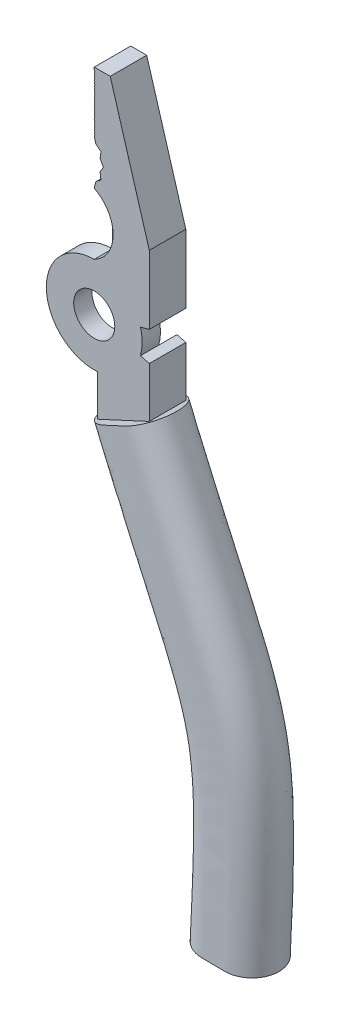
SolidWorks part; units mm, degrees
ref_plane "Front Plane" through (0, 0, 0) normal (0, 0, 1) x (1, 0, 0)
ref_plane "Top Plane" through (0, 0, 0) normal (0, 1, 0) x (1, 0, 0)
ref_plane "Right Plane" through (0, 0, 0) normal (1, 0, 0) x (0, 0, -1)
sketch "Sketch1" plane through (0, 0, 0) normal (0, 0, 1) x (1, 0, 0)
  line L0 (-6.1652, 3.7232) -> (-2.6652, 3.7232)
  line L1 (-2.6652, 3.7232) -> (5.9089, -25.0255)
  line L2 (-6.1652, 3.7232) -> (-6.1652, 3.2232)
  line L3 (-6.1652, 3.2232) -> (-6.0208, 2.9732)
  line L4 (-6.0208, 2.9732) -> (-6.1652, 2.7232)
  line L5 (-6.1652, 2.7232) -> (-6.0208, 2.4732)
  line L6 (-6.0208, 2.4732) -> (-6.1652, 2.2232)
  line L7 (-6.1652, 2.2232) -> (-6.0208, 1.9732)
  line L8 (-6.0208, 1.9732) -> (-6.1652, 1.7232)
  line L9 (-6.1652, 1.7232) -> (-6.0208, 1.4732)
  line L10 (-6.0208, 1.4732) -> (-6.1652, 1.2232)
  line L11 (-6.1652, 1.2232) -> (-6.0208, 0.9732)
  line L12 (-6.0208, 0.9732) -> (-6.1652, 0.7232)
  line L13 (-6.1652, 0.7232) -> (-6.0208, 0.4732)
  line L14 (-6.0208, 0.4732) -> (-6.1652, 0.2232)
  line L15 (-6.1652, 0.2232) -> (-6.0208, -0.0268)
  line L16 (-6.0208, -0.0268) -> (-6.1652, -0.2768)
  line L17 (-6.1652, -0.2768) -> (-6.0208, -0.5268)
  line L18 (-6.0208, -0.5268) -> (-6.1652, -0.7768)
  line L19 (-6.1652, -0.7768) -> (-6.0208, -1.0268)
  line L20 (-6.0208, -1.0268) -> (-6.1652, -1.2768)
  line L21 (-6.1652, -1.2768) -> (-6.0208, -1.5268)
  line L22 (-6.0208, -1.5268) -> (-6.1652, -1.7768)
  line L23 (-6.1652, -1.7768) -> (-6.0208, -2.0268)
  line L24 (-6.0208, -2.0268) -> (-6.1652, -2.2768)
  line L25 (-6.1652, -2.2768) -> (-6.0208, -2.5268)
  line L26 (-6.0208, -2.5268) -> (-6.1652, -2.7768)
  line L27 (-6.1652, -2.7768) -> (-6.0208, -3.0268)
  line L28 (-6.0208, -3.0268) -> (-6.1652, -3.2768)
  line L29 (-6.1652, -3.2768) -> (-6.0208, -3.5268)
  line L30 (-6.0208, -3.5268) -> (-6.1652, -3.7768)
  line L31 (-6.1652, -3.7768) -> (-6.0208, -4.0268)
  line L32 (-6.0208, -4.0268) -> (-6.1652, -4.2768)
  line L33 (-6.1652, -4.2768) -> (-6.0208, -4.5268)
  line L34 (-6.0208, -4.5268) -> (-6.1652, -4.7768)
  line L35 (-6.1652, -4.7768) -> (-6.0208, -5.0268)
  line L36 (-6.0208, -5.0268) -> (-6.1652, -5.2768)
  line L37 (-6.1652, -5.2768) -> (-6.0208, -5.5268)
  line L38 (-6.0208, -5.5268) -> (-6.1652, -5.7768)
  line L39 (-6.1652, -5.7768) -> (-6.0208, -6.0268)
  line L40 (-6.0208, -6.0268) -> (-6.1652, -6.2768)
  line L41 (-6.1652, -6.2768) -> (-6.0208, -6.5268)
  line L42 (-6.0208, -6.5268) -> (-6.1652, -6.7768)
  line L43 (-6.1652, -6.7768) -> (-6.0208, -7.0268)
  line L44 (-6.0208, -7.0268) -> (-6.1652, -7.2768)
  line L45 (-6.1652, -7.2768) -> (-6.0208, -7.5268)
  line L46 (-6.0208, -7.5268) -> (-6.1652, -7.7768)
  line L47 (-6.1652, -7.7768) -> (-6.0208, -8.0268)
  line L48 (-6.0208, -8.0268) -> (-6.1652, -8.2768)
  line L49 (-6.1652, -8.2768) -> (-6.0208, -8.5268)
  line L50 (-6.0208, -8.5268) -> (-6.1652, -8.7768)
  line L51 (-6.1652, -8.7768) -> (-6.0208, -9.0268)
  line L52 (-6.0208, -9.0268) -> (-6.1652, -9.2768)
  line L53 (-6.1652, -9.2768) -> (-6.1652, -19.2768) construction
  line L54 (-6.1652, -14.2768) -> (-4.1652, -14.2768) construction
  line L55 (-6.1652, -9.2768) -> (-5.8192, -10.684)
  line L56 (-5.8192, -10.684) -> (-4.6837, -11.5843)
  line L57 (-5.8192, -10.684) -> (-5.3144, -10.3599) construction
  line L58 (-4.6837, -11.5843) -> (-4.8852, -13.0193)
  line L59 (-4.8852, -13.0193) -> (-4.1652, -14.2768)
  line L60 (-4.1652, -14.2768) -> (-4.8852, -15.5344)
  line L61 (-4.8852, -15.5344) -> (-4.6837, -16.9694)
  line L62 (-4.6837, -16.9694) -> (-5.8192, -17.8696)
  line L63 (-5.8192, -17.8696) -> (-6.1652, -19.2768)
  line L64 (-6.1652, -19.2768) -> (-6.1652, -32.7768)
  line L65 (-6.1652, -32.7768) -> (-6.1652, -67.9794) construction
  line L66 (-5.4152, -53.75) -> (-5.4152, -62.75)
  line L67 (-5.4152, -62.75) -> (5.9089, -57.5121)
  line L68 (5.9089, -57.5121) -> (5.9089, -46.5121)
  line L69 (5.9089, -46.5121) -> (3.9771, -45.9944)
  line L70 (-6.1652, -43.2768) -> (3.9771, -45.9944) construction
  line L71 (-6.1652, -43.2768) -> (13.351, -43.2768) construction
  line L72 (5.9089, -40.0416) -> (3.9771, -40.5592)
  line L73 (5.9089, -40.0416) -> (5.9089, -25.0255)
  arc A0 (-6.1652, -9.2768) -> (-6.1652, -19.2768) centre (-11.4152, -14.2768) cw construction
  circle A1 centre (-6.1652, -43.2768) radius 10.5
  circle A2 centre (-6.1652, -43.2768) radius 4.5
  point P29 (-11.4152, -14.2768)
  dimension "D12" = 21
  dimension "D13" = 9
  dimension "D1" = 3.5
  dimension "D2" = 0.5
  dimension "D3" = 30
  dimension "D4" = 120
  dimension "D5" = 0.5
  dimension "D7" = 10
  dimension "D8" = 2
  dimension "D9" = 0.6
  dimension "D11" = 13.5
  dimension "D14" = 9
  dimension "D15" = 0.75
  dimension "D16" = 11
  dimension "D17" = 2
  dimension "D18" = 15
  dimension "D6" = 25
  dimension "D10" = 4
extrude "Boss-Extrude1" add sketch "Sketch1" against normal blind 8 contours A1 L72 L73 L1 L0 L2 L3 L4 L5 L6 L7 L8 L9 L10 L11 L12 L13 L14 L15 L16 L17 L18 L19 L20 L21 L22 L23 L24 L25 L26 L27 L28 L29 L30 L31 L32 L33 L34 L35 L36 L37 L38 L39 L40 L41 L42 L43 L44 L45 L46 L47 region at (-0.7768, -19.8519, 0)
extrude "Boss-Extrude2" add sketch "Sketch1<3>" against normal blind 4 contours A1 A2 region at (3.9506, -41.9451, 0)
sketch "Sketch1<3>" plane through (0, 0, 0) normal (0, 0, 1) x (1, 0, 0) same geometry as "Sketch1"
extrude "Boss-Extrude3" add sketch "Sketch1<4>" against normal blind 8 contours A1 L66 L67 L68 L69 region at (0.632, -55.1308, 0)
sketch "Sketch1<4>" plane through (0, 0, 0) normal (0, 0, 1) x (1, 0, 0) same geometry as "Sketch1"
sketch "Sketch2" plane through (0, 0, 0) normal (0, 0, 1) x (1, 0, 0)
  line L0 (-6.1652, -19.2768) -> (-6.1652, -32.7768) construction
  line L1 (-6.1652, -19.2768) -> (-6.1652, -32.7768)
  arc A0 (-6.1652, -19.2768) -> (-6.1652, -32.7768) centre (-9.5944, -26.0268) cw
extrude "Cut-Extrude1" cut sketch "Sketch2" against normal blind 4
draft "Draft1" type of draft neutral plane draft angle 1 faces to draft 1 face at (-4.0942, -26.0268, -4) neutral plane through (-6.1652, 0, -8) neutral plane normal (-1, 0, 0) parameters "D1"=1
draft "Draft2" type of draft neutral plane draft angle 30 faces to draft 1 face at (-4.0942, -26.0268, -3.9639) neutral plane through (-6.1652, 0, -8) neutral plane normal (-1, 0, 0) parameters "D1"=30
sketch "Sketch3" plane through (0, 3.7232, 0) normal (0, 1, 0) x (1, 0, 0)
  line L0 (-6.1652, 4.4645) -> (-2.6296, 8)
  line L1 (-6.1652, 8) -> (-6.1652, 0) construction
  line L2 (-6.1652, 8) -> (-2.6652, 8) construction
  line L3 (-6.1652, 8) -> (-2.6296, 8)
  line L4 (-6.1652, 8) -> (-6.1652, 4.4645)
  dimension "D1" = 5
extrude "Cut-Extrude2" cut sketch "Sketch3" along normal up to surface and the other way up to surface from offset 30 up to face at (-4.0942, -26.0268, -1.4022) other way up to face at (-4.0942, -26.0268, -1.4022) offset against normal yes
sketch "Sketch4" plane through (22.9551, -49.6274, 0) normal (0.4198, -0.9076, 0) x (0.9076, 0.4198, 0)
  line L0 (-31.2582, -4) -> (-19.2582, -4) construction
  line L1 (-31.2582, -8) -> (-31.2582, 0) construction
  line L2 (-27.5455, -1) -> (-22.5455, -1)
  line L3 (-27.5455, -7) -> (-22.5455, -7)
  arc A0 (-27.5455, -1) -> (-27.5455, -7) centre (-27.5455, -4) ccw
  arc A1 (-22.5455, -1) -> (-22.5455, -7) centre (-22.5455, -4) cw
  dimension "D2" = 3
  dimension "D1" = 5
ref_plane "Plane1" through (0, 0, -4) normal (0, 0, 1) x (1, 0, 0)
sketch "Sketch5" plane through (0, 0, -4) normal (0, 0, 1) x (1, 0, 0)
  line L0 (-2.0455, -61.1914) -> (2.4926, -59.0923) construction
  spline S0 degree 3 poles (0.2236, -60.1418) (21.7495, -111.2742) (24.2369, -103.0982) (21.8412, -151.6127) knots 0 0 0 0 1 1 1 1
  point P2 (20.1335, -171.8351)
  point P3 (21.8412, -151.6127)
sweep "Sweep1" add profiles "Sketch4" path "Sketch5"
sketch "Sketch5<2>" plane through (0, 0, -4) normal (0, 0, 1) x (1, 0, 0) same geometry as "Sketch5"
sketch "Sketch13" plane through (-2.2036, -151.2625, 0) normal (-0.0146, -0.9999, 0) x (0.9999, -0.0146, 0)
  line L4 (21.5473, -10) -> (26.5473, -10)
  line L5 (26.5473, 2) -> (21.5473, 2)
  line L6 (21.5473, -10) -> (26.5473, -10)
  line L7 (26.5473, 2) -> (21.5473, 2)
  arc A4 (21.5473, 2) -> (21.5473, -10) centre (21.5473, -4) ccw
  arc A5 (26.5473, -10) -> (26.5473, 2) centre (26.5473, -4) ccw
  arc A6 (21.5473, 2) -> (21.5473, -10) centre (21.5473, -4) ccw
  arc A7 (26.5473, -10) -> (26.5473, 2) centre (26.5473, -4) ccw
  dimension "D1" = 3
sweep "Sweep3" add profiles "Sketch13" path "Sketch5<3>"
sketch "Sketch5<3>" plane through (0, 0, -4) normal (0, 0, 1) x (1, 0, 0) same geometry as "Sketch5"
